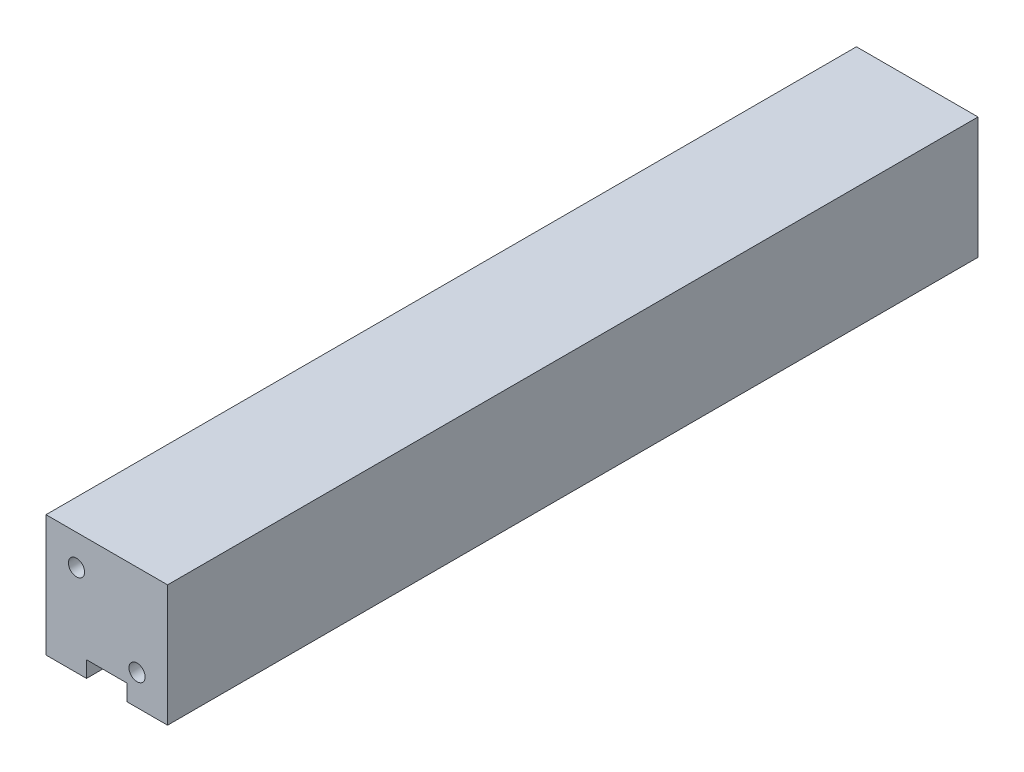
SolidWorks part; units mm, degrees
ref_plane "Alzado" through (0, 0, 0) normal (0, 0, 1) x (1, 0, 0)
ref_plane "Planta" through (0, 0, 0) normal (0, 1, 0) x (1, 0, 0)
ref_plane "Vista lateral" through (0, 0, 0) normal (1, 0, 0) x (0, 0, -1)
sketch "Croquis1" plane through (0, 0, 0) normal (0, 0, 1) x (1, 0, 0)
  line L1 (-15, -15) -> (15, -15)
  line L2 (-15, -15) -> (-15, 15)
  line L3 (-15, 15) -> (15, 15)
  line L4 (15, -15) -> (15, 15)
  line L5 (-15, -15) -> (15, 15) construction
  line L6 (-15, 15) -> (15, -15) construction
  point P0 (0, 0)
  dimension "D1" = 30
extrude "Saliente-Extruir1" add sketch "Croquis1" along normal blind 200
sketch "Croquis2" plane through (0, 0, 200) normal (0, 0, 1) x (1, 0, 0)
  line L0 (-15, 15) -> (15, -15) construction
  line L1 (-15, -15) -> (15, 15) construction
  circle A1 centre (-7.4706, 7.4706) radius 2
  circle A2 centre (7.4706, -7.4706) radius 2
  dimension "D1" = 10.565
extrude "Cortar-Extruir1" cut sketch "Croquis2" against normal blind 25
sketch "Croquis4" plane through (0, 0, 0) normal (0, 0, -1) x (-1, 0, 0)
  circle A0 centre (0, 0) radius 2
extrude "Cortar-Extruir3" cut sketch "Croquis4" against normal blind 25
sketch "Croquis5" plane through (0, 0, 0) normal (0, 0, -1) x (-1, 0, 0)
  line L0 (0, 0) -> (0, -15) construction
  line L1 (15, -15) -> (-15, -15) construction
  line L2 (0, 0) -> (15, 0) construction
  line L3 (-5, -19) -> (5, -19)
  line L4 (-5, -19) -> (-5, -11)
  line L5 (-5, -11) -> (5, -11)
  line L6 (5, -19) -> (5, -11)
  line L7 (-5, -19) -> (5, -11) construction
  line L8 (-5, -11) -> (5, -19) construction
  line L9 (15, 15) -> (15, -15) construction
  line L11 (11, -5.5) -> (19, -5.5)
  line L12 (11, -5.5) -> (11, 5.5)
  line L13 (11, 5.5) -> (19, 5.5)
  line L14 (19, -5.5) -> (19, 5.5)
  line L15 (11, -5.5) -> (19, 5.5) construction
  line L16 (11, 5.5) -> (19, -5.5) construction
  dimension "D1" = 10
  dimension "D2" = 8
  dimension "D3" = 8
  dimension "D4" = 11
extrude "Cortar-Extruir4" cut sketch "Croquis5" against normal blind 200
sketch "Croquis6" plane through (0, 0, 0) normal (0, 0, -1) x (-1, 0, 0)
  line L0 (11, -5.5) -> (15, -5.5) construction
  line L1 (11, 5.5) -> (11, -5.5) construction
  line L2 (15, 5.5) -> (11, 5.5) construction
  line L3 (11, -5.5) -> (15, -5.5)
  line L4 (11, 5.5) -> (11, -5.5)
  line L5 (15, 5.5) -> (11, 5.5)
  line L6 (15, 5.5) -> (15, -5.5)
extrude "Saliente-Extruir3" add sketch "Croquis6" against normal up to surface (200 mm away) from offset 90 up to face at (-4.3333, -4.3333, 200) offset against normal yes
sketch "Croquis7" plane through (0, 0, 0) normal (0, 0, -1) x (-1, 0, 0)
  line L0 (11, -5.5) -> (15, -5.5) construction
  line L1 (15, 5.5) -> (11, 5.5) construction
  line L2 (11, -5.5) -> (15, -5.5) construction
  line L3 (15, 5.5) -> (11, 5.5) construction
  line L4 (15, 5.5) -> (5, 5.5)
  line L5 (5, 5.5) -> (5, -5.5)
  line L6 (5, -5.5) -> (15, -5.5)
  line L7 (15, -5.5) -> (15, 5.5)
  dimension "D1" = 10
extrude "Cortar-Extruir5" cut sketch "Croquis7" against normal blind 90
